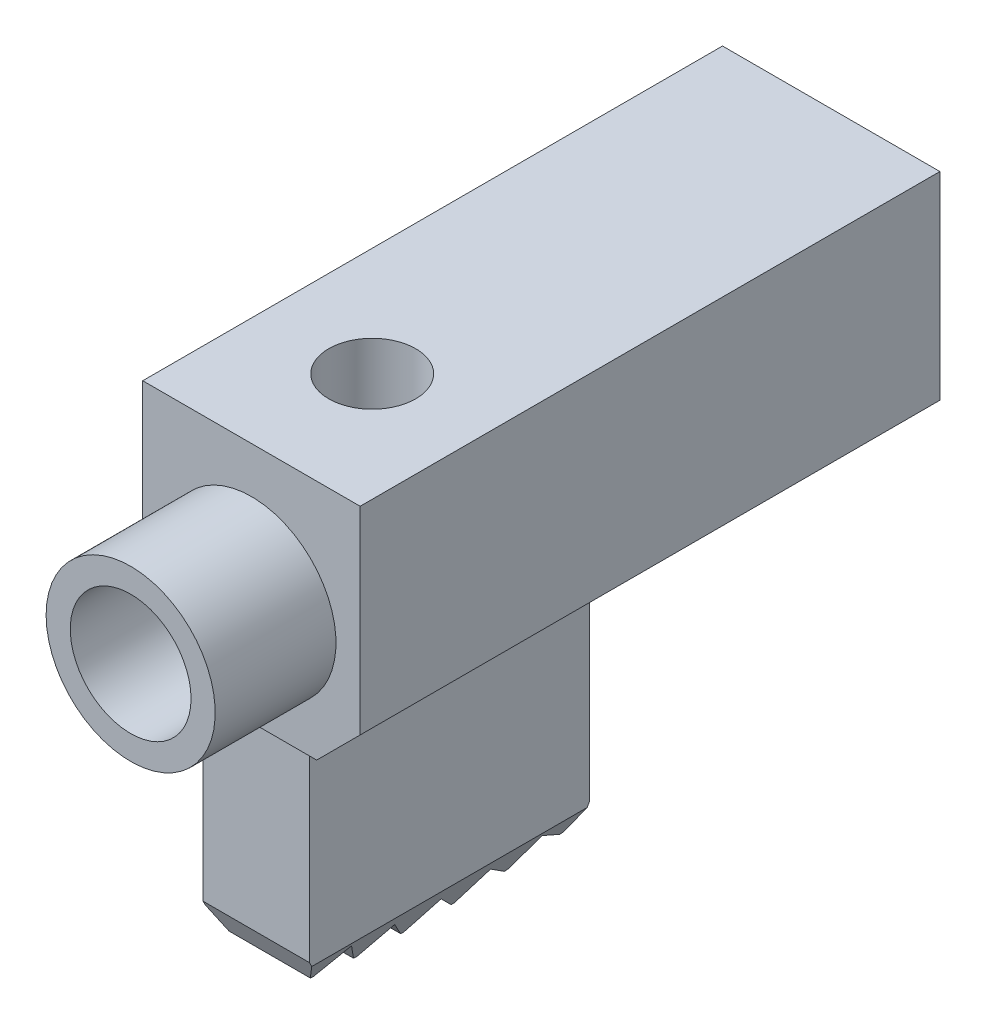
SolidWorks part; units mm, degrees
ref_plane "Front Plane" through (0, 0, 0) normal (0, 0, 1) x (1, 0, 0)
ref_plane "Top Plane" through (0, 0, 0) normal (0, 1, 0) x (1, 0, 0)
ref_plane "Right Plane" through (0, 0, 0) normal (1, 0, 0) x (0, 0, -1)
sketch "Sketch1" plane through (0, 0, 0) normal (0, 0, 1) x (1, 0, 0)
  line L0 (0, 0) -> (0, 2.9025) construction
  line L2 (-2.25, 2.7) -> (2.25, 2.7)
  line L3 (-2.25, 2.7) -> (-2.25, -2.3)
  line L4 (-2.25, -2.3) -> (2.25, -2.3)
  line L5 (2.25, 2.7) -> (2.25, -2.3)
  line L6 (-2.25, 2.7) -> (2.25, -2.3) construction
  line L7 (-2.25, -2.3) -> (2.25, 2.7) construction
  point P2 (0, 0.2)
  dimension "D1" = 4.5
  dimension "D2" = 5
  dimension "D3" = 2.7
extrude "Boss-Extrude1" add sketch "Sketch1" along normal blind 12
sketch "Sketch4" plane through (0, 0, 12) normal (0, 0, 1) x (1, 0, 0)
  circle A0 centre (0, 0) radius 1.75
  dimension "D1" = 3.5
extrude "Boss-Extrude3" add sketch "Sketch4" along normal offset from surface (2.5 mm away) 14.5 up to face at (0, 0.2, 0)
sketch "Sketch5" plane through (0, 0, 14.5) normal (0, 0, 1) x (1, 0, 0)
  circle A0 centre (0, 0) radius 1.25
  circle A1 centre (0, 0) radius 1.75 construction
  dimension "D1" = 2.5
extrude "Cut-Extrude1" cut sketch "Sketch5" against normal through all
ref_plane "Plane1" through (0, 0, 6.1) normal (0, 0, 1) x (1, 0, 0)
sketch "Sketch7" plane through (0, 0, 6.1) normal (0, 0, 1) x (1, 0, 0)
  line L0 (0, 0) -> (0, -4.1044) construction
  line L1 (-2.25, -2.3) -> (2.25, -2.3) construction
  line L2 (-1.1, -2.3) -> (1.1, -2.3)
  line L3 (-1.1, -2.3) -> (-1.1, -7)
  line L4 (-1.1, -7) -> (1.1, -7)
  line L5 (1.1, -2.3) -> (1.1, -7)
  line L6 (2.25, 2.7) -> (-2.25, 2.7) construction
  dimension "D1" = 2.2
  dimension "D2" = 9.7
extrude "Boss-Extrude4" add sketch "Sketch7" along normal blind 5.8
sketch "Sketch8" plane through (0, 0, 12) normal (0, 0, 1) x (1, 0, 0)
  line L0 (0, 0) -> (0, -7) construction
  line L1 (1.35, -2.3) -> (2.25, -1.4)
  line L2 (-2.25, -2.3) -> (2.25, -2.3) construction
  line L3 (2.25, -2.3) -> (2.25, 2.7) construction
  line L4 (2.25, -2.3) -> (2.25, -1.4)
  line L5 (-1.35, -2.3) -> (-2.25, -2.3)
  line L6 (1.35, -2.3) -> (2.25, -2.3)
  line L7 (-1.35, -2.3) -> (-2.25, -1.4)
  line L8 (-2.25, -2.3) -> (-2.25, -1.4)
  line L9 (-1.1, -7) -> (1.1, -7) construction
  dimension "D1" = 45
  dimension "D2" = 2.7
extrude "Cut-Extrude2" cut sketch "Sketch8" against normal through all
sketch "Sketch10" plane through (0, 0, 11.9) normal (0, 0, 1) x (1, 0, 0)
  line L0 (0, 0) -> (0, -7) construction
  line L1 (-1.1, -7) -> (1.1, -7) construction
  line L2 (1.1, -7) -> (1.1, -2.3) construction
  line L3 (-0.6381, -7) -> (-1.1, -7)
  line L4 (1.1, -7) -> (1.1, -6.2)
  line L6 (1.1, -6.2) -> (0.6381, -7)
  line L7 (0.6381, -7) -> (1.1, -7)
  line L8 (-1.35, -2.3) -> (1.35, -2.3) construction
  line L9 (-1.1, -6.2) -> (-0.6381, -7)
  line L10 (-1.1, -7) -> (-1.1, -6.2)
  dimension "D2" = 30
  dimension "D3" = 3.9
extrude "Cut-Extrude6" cut sketch "Sketch10" against normal through all
sketch "Sketch9" plane through (0, 0, 0) normal (1, 0, 0) x (0, 0, -1)
  line L0 (-11.9, -6.2) -> (-11.9, -2.3) construction
  line L2 (-9, 3) -> (-9, -7) construction
  line L3 (-9, 3) -> (-7.9547, -6.9452) construction
  line L4 (-9, -6.5) -> (-9.4881, -6.9881)
  line L5 (-9, -6.5) -> (-8.5119, -6.9881)
  line L7 (-6.1, -7) -> (-11.9, -7) construction
  line L9 (-11.9, -6.5703) -> (-11.9, -8)
  line L11 (-6.1, -6.5703) -> (-6.1, -8)
  line L12 (-11.9, -8) -> (-6.1, -8)
  line L14 (-6.1, -6.2) -> (-6.1, -2.3) construction
  line L15 (-11.9, -6.2) -> (-11.9, -2.3) construction
  line L16 (-9.4881, -6.9881) -> (-10.0324, -6.4437) construction
  arc A0 (-11.9, -6.5703) -> (-6.1, -6.5703) centre (-9, 3) ccw
  arc A1 (-9, -6.5) -> (-8.007, -6.448) centre (-9, 3) ccw construction
  circle A3 centre (-9, 3) radius 9.5 construction
  circle A4 centre (-9, 3) radius 10 construction
  point P13 (0.5, 3)
  point P16 (0.563, 5.9237)
  dimension "D2" = 10
  dimension "D3" = 6
  dimension "D1" = 2.9
  dimension "D5" = 1
  dimension "D4" = 0.5
extrude "Cut-Extrude3" cut sketch "Sketch9" against normal through all both and the other way through all contours L9 L12 L11 A0
extrude "Cut-Extrude4" cut sketch "Sketch9<3>" against normal through all both and the other way through all contours A0 region at (0, -6.8307, 9)
sketch "Sketch9<3>" plane through (0, 0, 0) normal (1, 0, 0) x (0, 0, -1) same geometry as "Sketch9"
pattern_circular "CirPattern3" count 60 every 6 about axis through (-2.25, 3, 9) along (1, 0, 0) skipping 8, 9, 10, 11, 12, 13 of "Cut-Extrude4"
pattern_circular "CirPattern4" [suppressed] count 4 every 6 of bodies 113
hole_wizard "Ø1.8 (1.8) Diameter Hole1" positions "Sketch13" profile "Sketch12" hole size "Ø1.8" standard "ANSI Metric"
sketch "Sketch13" plane through (0, 2.7, 0) normal (0, 1, 0) x (1, 0, 0)
  line L0 (0, 0) -> (0, -14.5) construction
  line L1 (1.1, -6.1) -> (-1.1, -6.1) construction
  point P0 (0, -9.5)
  dimension "D1" = 3.4
sketch "Sketch12" plane through (0, 2.7, 9.5) normal (1, 0, 0) x (0, 0, 1)
  line L0 (0, 0) -> (0, 8.7408)
  line L1 (0, 8.7408) -> (0.9, 8.2)
  line L2 (0.9, 8.2) -> (0.9, 0)
  line L5 (0.9, 0) -> (0, 0)
  line L10 (0, 8.7408) -> (-0.9, 8.2) construction
  line L11 (0, -6.35) -> (0, 107.95) construction
  dimension "Hole Dia." = 1.8
  dimension "Hole Depth" = 8.2
  dimension "Drill Angle" = 118
